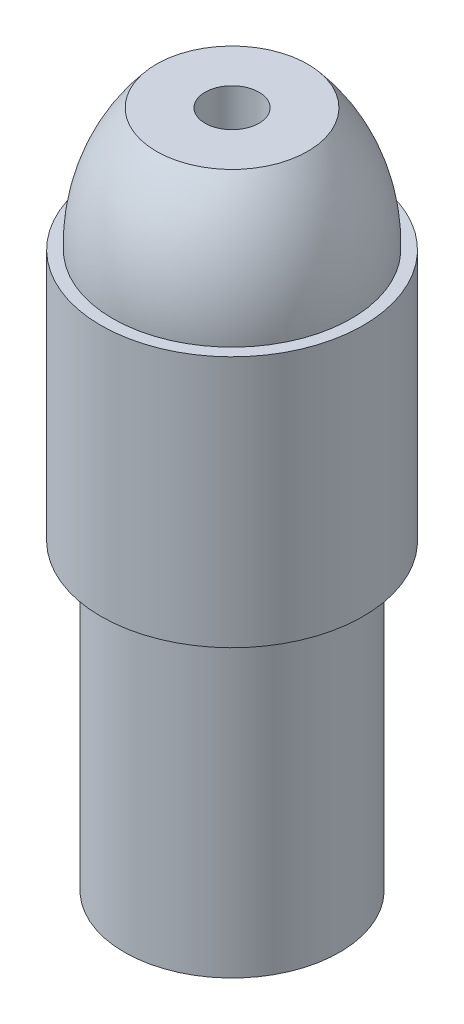
SolidWorks part; units mm, degrees
ref_plane "Front Plane" through (0, 0, 0) normal (0, 0, 1) x (1, 0, 0)
ref_plane "Top Plane" through (0, 0, 0) normal (0, 1, 0) x (1, 0, 0)
ref_plane "Right Plane" through (0, 0, 0) normal (1, 0, 0) x (0, 0, -1)
sketch "Sketch1" plane through (0, 0, 0) normal (0, 1, 0) x (1, 0, 0)
  circle A0 centre (0, 0) radius 4.69
  dimension "D1" = 9.38
extrude "Boss-Extrude1" add sketch "Sketch1" along normal blind 13.2
sketch "Sketch2" plane through (0, 13.2, 0) normal (0, 1, 0) x (1, 0, 0)
  circle A0 centre (0, 0) radius 5.718
extrude "Boss-Extrude2" add sketch "Sketch2" along normal blind 16.35
sketch "Sketch3" plane through (0, 0, 0) normal (0, 0, 1) x (1, 0, 0)
  line L0 (3.2971, 29.55) -> (5.718, 29.55)
  line L1 (5.718, 29.55) -> (-5.718, 29.55) construction
  line L2 (5.718, 29.55) -> (5.718, 24.1869)
  line L3 (5.718, 13.2) -> (5.718, 29.55) construction
  line L4 (5.718, 24.1869) -> (5.2027, 24.1869)
  arc A0 (3.2971, 29.55) -> (5.2027, 24.1869) centre (-2.6869, 24.4037) cw
ref_axis "Axis1" through (0, 29.55, 0) along (0, -1, 0)
revolve "Cut-Revolve1" cut sketch "Sketch3" angle 360 about axis through (0, 29.55, 0) along (0, -1, 0)
sketch "Sketch4" plane through (0, 0, 0) normal (0, -1, 0) x (1, 0, 0)
  circle A0 centre (0, 0) radius 1.175
  dimension "D1" = 2.35
extrude "Cut-Extrude1" cut sketch "Sketch4" against normal through all
